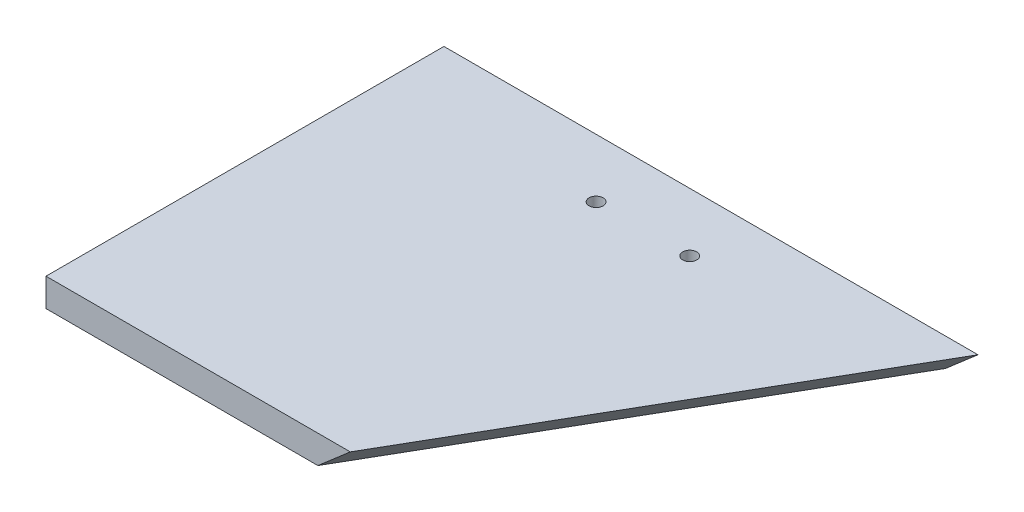
SolidWorks part; units mm, degrees
ref_plane "Front" through (0, 0, 0) normal (0, 0, 1) x (1, 0, 0)
ref_plane "Top" through (0, 0, 0) normal (0, 1, 0) x (1, 0, 0)
ref_plane "Right" through (0, 0, 0) normal (1, 0, 0) x (0, 0, -1)
sketch "Sketch1" plane through (0, 0, 0) normal (0, 1, 0) x (1, 0, 0)
  line L0 (0, 0) -> (49.0748, 85)
  line L1 (0, 0) -> (-65, 0)
  line L3 (0, 85) -> (-65, 85)
  line L4 (-65, 0) -> (-65, 85)
  line L5 (49.0748, 85) -> (0, 85)
  dimension "D1" = 65
  dimension "D2" = 85
  dimension "D3" = 120
extrude "Boss-Extrude1" add sketch "Sketch1" along normal blind 6
sketch "Sketch2" plane through (0, 6, 0) normal (0, 1, 0) x (1, 0, 0)
  line L0 (-65, 85) -> (-65, 0) construction
  line L1 (49.0748, 85) -> (-65, 85) construction
  circle A0 centre (-20, 72.5) radius 1.5
  circle A1 centre (0, 72.5) radius 1.5
  dimension "D1" = 3
  dimension "D2" = 20
  dimension "D3" = 45
  dimension "D4" = 12.5
extrude "Cut-Extrude1" cut sketch "Sketch2" against normal through all
chamfer "Chamfer1" distance 6 angle 45 1 edges at (24.5374, 0, -42.5)
